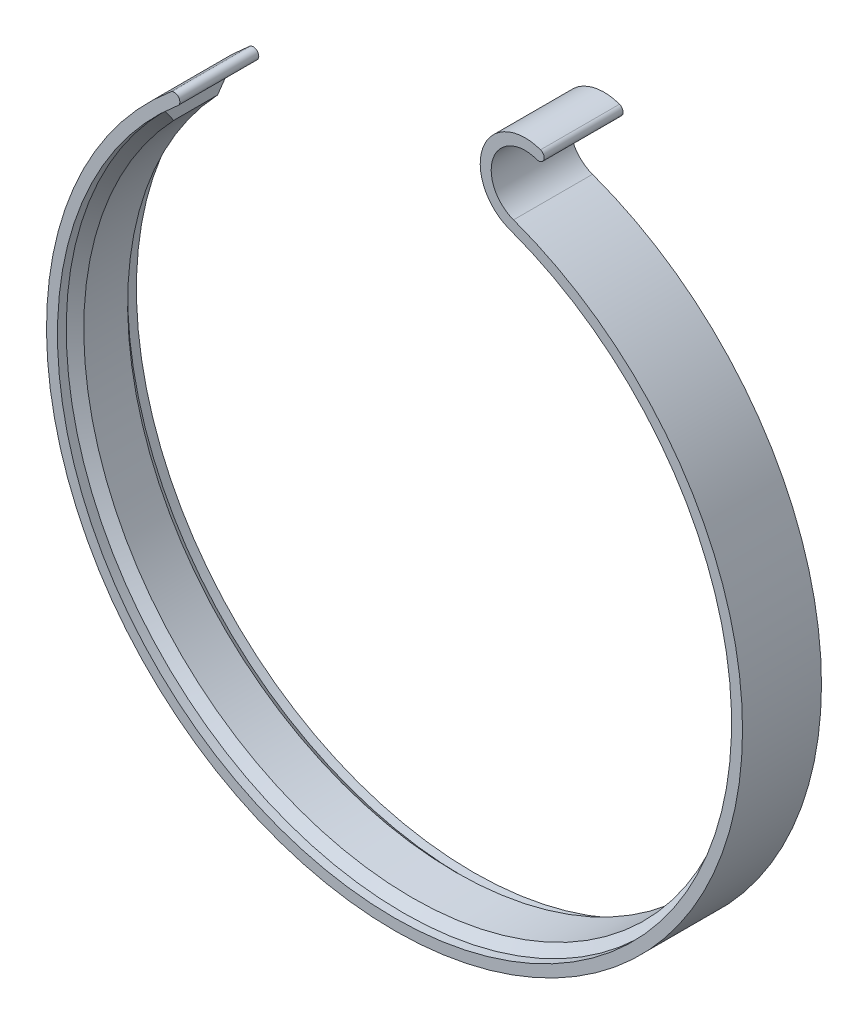
SolidWorks part; units mm, degrees
ref_plane "Front Plane" through (0, 0, 0) normal (0, 0, 1) x (1, 0, 0)
ref_plane "Top Plane" through (0, 0, 0) normal (0, 1, 0) x (1, 0, 0)
ref_plane "Right Plane" through (0, 0, 0) normal (1, 0, 0) x (0, 0, -1)
sketch "Sketch1" plane through (0, 0, 0) normal (0, 0, 1) x (1, 0, 0)
  line L0 (0, 0) -> (0, 98.4093) construction
  line L4 (29.79, 81.8472) -> (0, 0) construction
  line L5 (0, 0) -> (-59.8253, 71.2971) construction
  arc A0 (-49.3982, 58.8705) -> (26.2842, 72.2154) centre (0, 0) ccw
  arc A1 (-51.0052, 60.7856) -> (27.1393, 74.5646) centre (0, 0) ccw
  arc A4 (26.2842, 72.2154) -> (33.2957, 91.4791) centre (29.79, 81.8472) cw
  arc A5 (27.1393, 74.5646) -> (32.4406, 89.1298) centre (29.79, 81.8472) cw
  arc A6 (33.2957, 91.4791) -> (32.5369, 89.0992) centre (32.8681, 90.3045) cw
  arc A7 (32.4406, 89.1298) -> (33.2957, 91.4791) centre (32.8681, 90.3045) ccw
  arc A10 (-49.3982, 58.8705) -> (-49.0561, 60.3282) centre (-50.2017, 59.8281) ccw
  arc A11 (-49.0561, 60.3282) -> (-51.0052, 60.7856) centre (-50.2017, 59.8281) ccw
  dimension "D1" = 2.5
  dimension "D2" = 153.7
  dimension "D3" = 9
  dimension "D4" = 40
  dimension "D6" = 2.5
  dimension "D5" = 20
extrude "Boss-Extrude1" add sketch "Sketch1" along normal blind 18 contours A10 A11 A1 A5 A7 A6 A4 A0 region at (13.7505, -77.9832, 0)
sketch "Sketch2" plane through (0, 0, 0) normal (1, 0, 0) x (0, 0, -1)
  line L1 (-15, -73.8981) -> (-15, -69.3473) construction
  line L7 (-14, -74.85) -> (-16, -76.85)
  line L8 (-16, -76.85) -> (-2, -76.85)
  line L9 (-14, -74.85) -> (-4, -74.85)
  line L10 (-18, -69.3473) -> (0, -69.3473) construction
  line L12 (-9, -69.3473) -> (-9, -89.1861) construction
  line L13 (-4, -74.85) -> (-2, -76.85)
  line L14 (0, 0) -> (-38.791, 0) construction
  line L15 (-18, 74.5646) -> (-18, -79.35) construction
  line L16 (0, -79.35) -> (0, 74.5646) construction
  point P17 (-9, -74.85)
  point P18 (-9, -76.85)
  dimension "D1" = 45
  dimension "D2" = 3
  dimension "D3" = 2
  dimension "D4" = 1
  dimension "D5" = 76.85
revolve "Revolve1" add sketch "Sketch2" angle 155 about L14 other way angle 135
chamfer "Chamfer1" distance 2 angle 45 2 edges at (31.633, 67.8371, 9) (-52.9269, 52.9269, 9)
